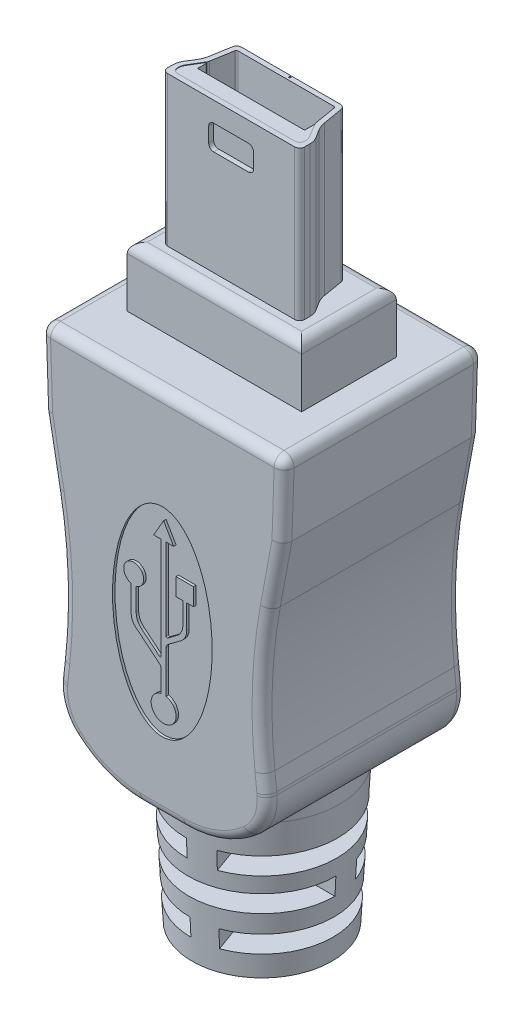
SolidWorks part; units mm, degrees
ref_plane "Front Plane" through (0, 0, 0) normal (0, 0, 1) x (1, 0, 0)
ref_plane "Top Plane" through (0, 0, 0) normal (0, 1, 0) x (1, 0, 0)
ref_plane "Right Plane" through (0, 0, 0) normal (1, 0, 0) x (0, 0, -1)
sketch "Sketch1" plane through (0, 0, 0) normal (0, 0, 1) x (1, 0, 0)
  line L0 (-1.1038, 0) -> (1.1038, 0)
  line L2 (5.3251, 3.5365) -> (5.2287, 4.4229)
  line L3 (-6.223, 18.796) -> (-6.096, 14.986)
  line L4 (-6.096, 14.986) -> (-5.5046, 11.7926)
  line L5 (6.223, 18.796) -> (-6.223, 18.796)
  line L6 (0, 0) -> (0, 13.2322) construction
  line L8 (-5.3251, 3.5365) -> (-5.2287, 4.4229)
  line L9 (6.223, 18.796) -> (6.096, 14.986)
  line L10 (6.096, 14.986) -> (5.5046, 11.7926)
  arc A0 (5.2287, 4.4229) -> (5.5046, 11.7926) centre (30.48, 7.1676) cw
  arc A1 (-5.2287, 4.4229) -> (-5.5046, 11.7926) centre (-30.48, 7.1676) ccw
  arc A2 (1.1038, 0) -> (4.5089, 1.3102) centre (1.1038, 5.08) ccw
  arc A3 (-4.5089, 1.3102) -> (-1.1038, 0) centre (-1.1038, 5.08) ccw
  arc A4 (5.3378, 3.4027) -> (5.3251, 3.5365) centre (0.2748, 2.9876) ccw
  arc A5 (-5.3378, 3.4027) -> (-5.3251, 3.5365) centre (-0.2748, 2.9876) cw
  arc A6 (-5.3378, 3.4027) -> (-4.5089, 1.3102) centre (-2.8063, 3.1951) ccw
  arc A7 (4.5089, 1.3102) -> (5.3378, 3.4027) centre (2.8063, 3.1951) ccw
  point P14 (0, 18.796)
  point P16 (4.5971, 1.1293)
  point P17 (4.826, 8.128)
  point P20 (-4.826, 8.128)
  point P23 (4.5554, 0)
  point P26 (-4.5554, 0)
  point P29 (5.461, 2.286)
  point P32 (-5.461, 2.286)
  dimension "D9" = 25.4
  dimension "D10" = 5.08
  dimension "D7" = 2.54
  dimension "D1" = 9.652
  dimension "D2" = 12.446
  dimension "D3" = 12.192
  dimension "D4" = 3.81
  dimension "D5" = 18.796
  dimension "D6" = 10.922
  dimension "D8" = 2.286
extrude "Boss-Extrude1" add sketch "Sketch1" along normal blind 10.16
fillet "Fillet1" radius 0.508 34 edges at (6.223, 18.796, 5.08) (-6.223, 18.796, 5.08) (6.1595, 16.891, 0) (0, 18.796, 0) (-6.1595, 16.891, 0) (-5.8003, 13.3893, 0) (-5.0978, 8.1178, 0) (-5.2769, 3.9797, 0) (-5.3319, 3.4696, 0) (-2.928, 0.3389, 0) (0, 0, 0) (2.928, 0.3389, 0) (5.3319, 3.4696, 0) (5.2769, 3.9797, 0) (5.0978, 8.1178, 0) (5.8003, 13.3893, 0) (5.0978, 8.1178, 10.16) (5.2769, 3.9797, 10.16) (5.3319, 3.4696, 10.16) (2.928, 0.3389, 10.16) (0, 0, 10.16) (-2.928, 0.3389, 10.16) (-5.3319, 3.4696, 10.16) (-5.2769, 3.9797, 10.16) (-5.0978, 8.1178, 10.16) (-5.8003, 13.3893, 10.16) (-6.1595, 16.891, 10.16) (0, 18.796, 10.16) (6.1595, 16.891, 10.16) (5.8003, 13.3893, 10.16) (-5.1678, 2.2596, 0) (5.1678, 2.2596, 0) (5.1678, 2.2596, 10.16) (-5.1678, 2.2596, 10.16)
sketch "Sketch2" plane through (0, 0, 0) normal (0, 0, -1) x (-1, 0, 0)
  ellipse E0 centre (0, 8.636) end of major axis (0, 3.556) minor radius 2.54
  dimension "D1" = 10.16
  dimension "D2" = 5.08
  dimension "D3" = 3.556
extrude "Cut-Extrude1" cut sketch "Sketch2" against normal blind 0.127
ref_plane "Plane1" through (0, 0, 5.08) normal (0, 0, -1) x (-1, 0, 0)
mirror "Mirror1" about plane through (0, 0, 5.08) normal (0, 0, -1) of "Cut-Extrude1"
sketch "Sketch3" plane through (0, 0, 10.033) normal (0, 0, 1) x (1, 0, 0)
  line L0 (0.0639, 12.685) -> (0.0639, 4.5092) construction
  line L1 (0.0639, 13.1276) -> (-0.4441, 12.2477)
  line L2 (0.6989, 10.9791) -> (1.5879, 10.9791)
  line L3 (0.6989, 10.9791) -> (0.6989, 10.0901)
  line L4 (0.6989, 10.5346) -> (1.5879, 10.5346) construction
  line L5 (0.6989, 10.0901) -> (1.0469, 10.0901)
  line L6 (1.5879, 10.9791) -> (1.5879, 10.0901)
  line L7 (-0.0631, 5.4334) -> (-0.0631, 6.5244)
  line L8 (0.1909, 5.4334) -> (0.1909, 7.5804)
  line L9 (-0.4441, 12.2477) -> (-0.0631, 12.2477)
  line L10 (0.5719, 12.2477) -> (0.0639, 13.1276)
  line L11 (0.0639, 13.1276) -> (0.0639, 12.7432) construction
  line L12 (1.0469, 10.0901) -> (1.2399, 10.0901) construction
  line L13 (0.272, 8.0523) -> (0.7391, 8.3989)
  line L14 (1.2399, 10.0901) -> (1.2399, 8.8701)
  line L15 (0.932, 8.2582) -> (0.2935, 7.7844)
  line L16 (-0.1463, 7.0423) -> (-1.0566, 7.7949)
  line L17 (-1.3331, 8.3822) -> (-1.3331, 9.5347)
  line L18 (-1.5871, 8.8632) -> (-1.3331, 8.8632) construction
  line L19 (-0.1552, 6.7202) -> (-1.3659, 7.721)
  line L20 (-1.5871, 8.1908) -> (-1.5871, 9.5347)
  line L21 (-1.4601, 8.8632) -> (-1.4601, 9.2602) construction
  line L22 (1.0469, 10.0901) -> (1.0469, 9.0108)
  line L23 (0.1909, 8.1908) -> (-0.0631, 8.1908) construction
  line L24 (0.0639, 8.1908) -> (0.0639, 8.5498) construction
  line L25 (0.1909, 12.2477) -> (0.5719, 12.2477)
  line L26 (1.2399, 10.0901) -> (1.5879, 10.0901)
  line L27 (-0.0631, 7.0814) -> (-0.0631, 12.2477)
  line L28 (0.1909, 8.0931) -> (0.1909, 12.2477)
  line L29 (1.1434, 10.0901) -> (1.1434, 10.172) construction
  line L30 (1.1434, 10.5346) -> (1.1434, 10.4705) construction
  arc A0 (-0.0631, 5.4334) -> (0.1909, 5.4334) centre (0.0639, 4.8112) ccw
  arc A1 (-1.3331, 9.5347) -> (-1.5871, 9.5347) centre (-1.4601, 10.0266) ccw
  arc A2 (1.2399, 8.8701) -> (0.932, 8.2582) centre (0.4779, 8.8701) cw
  arc A3 (1.0469, 9.0108) -> (0.7391, 8.3989) centre (0.2849, 9.0108) cw
  arc A4 (-1.3331, 8.3822) -> (-1.0566, 7.7949) centre (-0.5711, 8.3822) ccw
  arc A5 (-1.5871, 8.1908) -> (-1.3659, 7.721) centre (-0.9775, 8.1908) ccw
  arc A6 (-0.0631, 7.0814) -> (-0.1463, 7.0423) centre (-0.1139, 7.0814) cw
  arc A7 (0.1909, 8.0931) -> (0.272, 8.0523) centre (0.2417, 8.0931) ccw
  arc A8 (0.2935, 7.7844) -> (0.1909, 7.5804) centre (0.4449, 7.5804) ccw
  arc A9 (-0.0631, 6.5244) -> (-0.1552, 6.7202) centre (-0.3171, 6.5244) ccw
  point P2 (0.0081, 8.6549)
  dimension "D1" = 1.27
  dimension "D2" = 1.016
  dimension "D12" = 0.762
  dimension "D15" = 0.762
  dimension "D17" = 0.762
  dimension "D19" = 0.0508
  dimension "D20" = 0.254
  dimension "D3" = 0.889
  dimension "D4" = 0.889
  dimension "D5" = 1.016
  dimension "D6" = 1.016
  dimension "D7" = 1.016
  dimension "D8" = 0.508
  dimension "D9" = 1.397
  dimension "D10" = 0.508
  dimension "D11" = 0.254
  dimension "D13" = 0.254
  dimension "D14" = 50.42
  dimension "D18" = 0.254
extrude "Boss-Extrude2" add sketch "Sketch3" along normal blind 0.127
sketch "Sketch5" plane through (0, 0, 0) normal (0, -1, 0) x (1, 0, 0)
  line L0 (0, 9.652) -> (0, 0.508) construction
  line L1 (1.1038, 9.652) -> (-1.1038, 9.652) construction
  line L2 (-1.1038, 0.508) -> (1.1038, 0.508) construction
  circle A0 centre (0, 5.08) radius 3.937
  dimension "D1" = 7.874
extrude "Boss-Extrude3" add sketch "Sketch5" along normal blind 7.112 draft 3 and the other way blind 1.143
ref_axis "Axis1" through (0, 0, 5.08) along (0, -1, 0)
sketch "Sketch6" plane through (0, 0, 0) normal (1, 0, 0) x (0, 0, -1)
  line L0 (-5.08, 0) -> (-5.08, -7.112) construction
  line L1 (-7.366, -2.4384) -> (-11.069, -2.4384)
  line L2 (-7.366, -2.4384) -> (-7.366, -1.524)
  line L3 (-7.366, -1.524) -> (-11.069, -1.524)
  line L4 (-11.069, -2.4384) -> (-11.069, -1.524)
  line L5 (-2.794, -2.4384) -> (1.3873, -2.4384)
  line L6 (-2.794, -2.4384) -> (-2.794, -1.524)
  line L7 (-2.794, -1.524) -> (1.3873, -1.524)
  line L8 (1.3873, -2.4384) -> (1.3873, -1.524)
  line L9 (-8.8591, 0) -> (-1.3009, 0) construction
  line L11 (-2.794, -5.1054) -> (0.7668, -5.1054)
  line L12 (-2.794, -5.1054) -> (-2.794, -6.0198)
  line L13 (-2.794, -6.0198) -> (0.7668, -6.0198)
  line L14 (0.7668, -5.1054) -> (0.7668, -6.0198)
  line L15 (-7.366, -5.1054) -> (-10.6323, -5.1054)
  line L16 (-7.366, -5.1054) -> (-7.366, -6.0198)
  line L17 (-7.366, -6.0198) -> (-10.6323, -6.0198)
  line L18 (-10.6323, -5.1054) -> (-10.6323, -6.0198)
  dimension "D1" = 2.286
  dimension "D2" = 2.286
  dimension "D3" = 1.524
  dimension "D4" = 1.524
  dimension "D5" = 0.9144
  dimension "D6" = 0.9144
  dimension "D7" = 0.9144
  dimension "D8" = 0.9144
  dimension "D9" = 2.667
  dimension "D10" = 2.667
  dimension "D11" = 2.286
  dimension "D12" = 2.286
revolve "Cut-Revolve1" cut sketch "Sketch6" angle 160 about axis through (0, 0, 5.08) along (0, -1, 0)
sketch "Sketch7" plane through (0, 0, 5.08) normal (0, 0, -1) x (-1, 0, 0)
  line L0 (3.8092, -2.4384) -> (0, -2.4384) construction
  line L1 (-2.286, -3.2512) -> (-5.6214, -3.2512)
  line L2 (-2.286, -3.2512) -> (-2.286, -4.1656)
  line L3 (-2.286, -4.1656) -> (-5.6214, -4.1656)
  line L4 (-5.6214, -3.2512) -> (-5.6214, -4.1656)
  line L5 (2.286, -3.2512) -> (5.8067, -3.2512)
  line L6 (2.286, -3.2512) -> (2.286, -4.1656)
  line L7 (2.286, -4.1656) -> (5.8067, -4.1656)
  line L8 (5.8067, -3.2512) -> (5.8067, -4.1656)
  line L9 (0, -2.4384) -> (-3.8092, -2.4384) construction
  line L10 (0, 0) -> (0, -7.112) construction
  dimension "D1" = 0.9144
  dimension "D2" = 0.9144
  dimension "D3" = 0.8128
  dimension "D4" = 0.8128
  dimension "D5" = 2.286
  dimension "D6" = 2.286
revolve "Cut-Revolve2" cut sketch "Sketch7" angle 160 about axis through (0, 0, 5.08) along (0, -1, 0)
sketch "Sketch8" plane through (0, 18.796, 0) normal (0, 1, 0) x (1, 0, 0)
  line L0 (-5.6978, -5.08) -> (-2.3849, -5.08) construction
  line L1 (-4.445, -2.6796) -> (4.445, -2.6796)
  line L2 (-4.445, -2.6796) -> (-4.445, -7.5056)
  line L3 (-4.445, -7.5056) -> (4.445, -7.5056)
  line L4 (4.445, -2.6796) -> (4.445, -7.5056)
  line L5 (-5.6978, -0.508) -> (-5.6978, -9.652) construction
  line L6 (4.445, -5.0926) -> (3.1929, -5.0926) construction
  line L7 (0, -0.508) -> (0, -1.2138) construction
  line L8 (5.6978, -0.508) -> (-5.6978, -0.508) construction
  line L9 (0, -7.5056) -> (0, -6.276) construction
  dimension "D1" = 8.89
  dimension "D2" = 4.826
extrude "Boss-Extrude4" add sketch "Sketch8" along normal blind 3.048
fillet "Fillet2" radius 0.508 4 edges at (0, 21.844, 2.6796) (4.445, 21.844, 5.0926) (0, 21.844, 7.5056) (-4.445, 21.844, 5.0926)
sketch "Sketch9" plane through (0, 21.844, 0) normal (0, 1, 0) x (1, 0, 0)
  line L0 (-3.4504, -5.0926) -> (-2.8204, -5.0926) construction
  line L1 (-2.5164, -3.6058) -> (2.5164, -3.6058)
  line L2 (-3.4927, -6.1299) -> (-3.4927, -6.3998)
  line L3 (0, -6.6538) -> (3.2387, -6.6538)
  line L4 (0, -6.6538) -> (-3.2387, -6.6538)
  line L5 (0, -3.6058) -> (0, -4.6543) construction
  line L6 (0, -3.1876) -> (0, -3.6834) construction
  line L7 (3.937, -3.1876) -> (-3.937, -3.1876) construction
  line L8 (-3.937, -5.0926) -> (-3.4504, -5.0926) construction
  line L9 (-3.937, -3.1876) -> (-3.937, -6.9976) construction
  line L10 (-2.7668, -3.817) -> (-2.9417, -4.8408)
  line L11 (-3.4927, -5.1298) -> (-3.4927, -6.6538) construction
  line L12 (-3.1218, -5.3082) -> (-3.3649, -5.6908)
  line L13 (3.4927, -6.1299) -> (3.4927, -6.3998)
  line L14 (3.1218, -5.3082) -> (3.3649, -5.6908)
  line L15 (2.7668, -3.817) -> (2.9417, -4.8408)
  line L16 (-2.4521, -3.8598) -> (2.4521, -3.8598)
  line L17 (2.5272, -3.9231) -> (2.727, -5.0926)
  line L18 (-2.727, -5.0926) -> (-2.727, -5.6378)
  line L19 (-2.5272, -3.9231) -> (-2.727, -5.0926)
  line L20 (-2.727, -5.6378) -> (2.727, -5.6378)
  line L21 (2.727, -5.6378) -> (2.727, -5.0926)
  arc A0 (3.2387, -6.6538) -> (3.4927, -6.3998) centre (3.2387, -6.3998) ccw
  arc A1 (2.7668, -3.817) -> (2.5164, -3.6058) centre (2.5164, -3.8598) ccw
  arc A2 (-3.4927, -6.3998) -> (-3.2387, -6.6538) centre (-3.2387, -6.3998) ccw
  arc A3 (-2.7668, -3.817) -> (-2.5164, -3.6058) centre (-2.5164, -3.8598) cw
  arc A4 (2.4521, -3.8598) -> (2.5272, -3.9231) centre (2.4521, -3.936) cw
  arc A5 (-2.5272, -3.9231) -> (-2.4521, -3.8598) centre (-2.4521, -3.936) cw
  arc A6 (3.1218, -5.3082) -> (2.9417, -4.8408) centre (4.1935, -4.6269) cw
  arc A7 (-2.9417, -4.8408) -> (-3.1218, -5.3082) centre (-4.1935, -4.6269) cw
  arc A8 (3.4927, -6.1299) -> (3.3649, -5.6908) centre (2.6741, -6.1299) ccw
  arc A9 (-3.3649, -5.6908) -> (-3.4927, -6.1299) centre (-2.6741, -6.1299) ccw
  point P30 (3.4927, -6.6538)
  point P33 (2.7307, -3.6058)
  point P39 (-2.7307, -3.6058)
  point P46 (2.9847, -5.0926)
  point P49 (-2.9847, -5.0926)
  point P52 (3.4927, -5.8918)
  point P55 (-3.4927, -5.8918)
  dimension "D7" = 0.254
  dimension "D8" = 0.0762
  dimension "D9" = 1.27
  dimension "D10" = 0.8186
  dimension "D1" = 0.254
  dimension "D2" = 0.254
  dimension "D3" = 0.762
  dimension "D4" = 0.254
  dimension "D5" = 0.254
  dimension "D6" = 1.016
extrude "Boss-Extrude5" add sketch "Sketch9" along normal blind 7.62 separate body
sketch "Sketch10" plane through (0, 29.464, 0) normal (0, 1, 0) x (1, 0, 0)
  line L0 (-2.727, -5.0926) -> (-3.166, -5.8219)
  line L1 (-3.2387, -6.0839) -> (-3.2387, -6.1458)
  line L2 (-2.9847, -6.3998) -> (2.9847, -6.3998)
  line L3 (0, -6.3998) -> (0, -4.3507) construction
  line L4 (3.2387, -6.0839) -> (3.2387, -6.1458)
  line L5 (2.727, -5.0926) -> (-2.727, -5.0926)
  line L6 (2.727, -5.0926) -> (3.166, -5.8219)
  line L11 (-3.2387, -6.6538) -> (3.2387, -6.6538) construction
  arc A0 (3.2387, -6.1458) -> (2.9847, -6.3998) centre (2.9847, -6.1458) cw
  arc A1 (-3.2387, -6.1458) -> (-2.9847, -6.3998) centre (-2.9847, -6.1458) ccw
  arc A2 (-3.166, -5.8219) -> (-3.2387, -6.0839) centre (-2.7307, -6.0839) ccw
  arc A3 (3.2387, -6.0839) -> (3.166, -5.8219) centre (2.7307, -6.0839) ccw
  point P15 (0, -5.0926)
  point P20 (-3.2387, -5.9428)
  point P23 (3.2387, -5.9428)
  dimension "D1" = 0.508
  dimension "D3" = 0.254
extrude "Cut-Extrude2" cut sketch "Sketch10" against normal blind 0.0254
sketch "Sketch11" plane through (0, 29.4386, 0) normal (0, 1, 0) x (1, 0, 0)
  line L0 (-2.765, -5.1557) -> (-2.727, -5.1557)
  line L1 (-2.727, -5.0926) -> (-3.166, -5.8219) construction
  line L2 (-2.765, -5.1557) -> (-2.727, -5.0926)
  line L3 (-2.727, -5.0926) -> (-2.727, -5.1557)
  line L4 (-2.727, -5.0926) -> (-2.727, -5.6378) construction
  line L5 (2.727, -5.0926) -> (2.765, -5.1557)
  line L6 (3.166, -5.8219) -> (2.727, -5.0926) construction
  line L7 (2.727, -5.0926) -> (2.727, -5.1557)
  line L8 (2.727, -5.1557) -> (2.765, -5.1557)
extrude "Cut-Extrude3" cut sketch "Sketch11" against normal up to surface (7.5946 mm away) up to face at (0, 21.844, 5.0926)
fillet "Fillet3" radius 0.254 2 edges at (-2.727, 25.654, 5.0926) (2.727, 25.654, 5.0926)
fillet "Fillet4" radius 0.0508 2 edges at (2.727, 25.6413, 5.1557) (-2.727, 25.6413, 5.1557)
sketch "Sketch12" plane through (0, 0, 6.6538) normal (0, 0, 1) x (1, 0, 0)
  line L0 (-3.2387, 29.464) -> (3.2387, 29.464) construction
  line L1 (-0.889, 27.178) -> (0.889, 27.178)
  line L2 (-1.143, 27.432) -> (-1.143, 28.194)
  line L3 (-0.889, 28.448) -> (0.889, 28.448)
  line L4 (1.143, 27.432) -> (1.143, 28.194)
  line L5 (0, 29.464) -> (0, 29.0468) construction
  line L6 (0, 28.448) -> (0, 27.9499) construction
  arc A0 (0.889, 28.448) -> (1.143, 28.194) centre (0.889, 28.194) cw
  arc A1 (0.889, 27.178) -> (1.143, 27.432) centre (0.889, 27.432) ccw
  arc A2 (-0.889, 27.178) -> (-1.143, 27.432) centre (-0.889, 27.432) cw
  arc A3 (-0.889, 28.448) -> (-1.143, 28.194) centre (-0.889, 28.194) ccw
  point P13 (1.143, 28.448)
  point P16 (1.143, 27.178)
  point P19 (-1.143, 27.178)
  dimension "D4" = 0.254
  dimension "D1" = 2.286
  dimension "D2" = 1.27
  dimension "D3" = 1.016
extrude "Cut-Extrude4" cut sketch "Sketch12" against normal blind 0.254
sketch "Sketch13" plane through (0, 0, 5.6378) normal (0, 0, -1) x (-1, 0, 0)
  line L0 (2.727, 21.844) -> (-2.727, 21.844)
  line L1 (-2.727, 29.1784) -> (-1.711, 29.1784)
  line L2 (2.0666, 27.9462) -> (2.0666, 29.153)
  line L3 (1.838, 29.1784) -> (1.838, 27.9716)
  line L4 (1.838, 27.9716) -> (-1.711, 27.9716)
  line L5 (-1.711, 27.9716) -> (-1.711, 29.1784)
  line L6 (1.838, 29.1784) -> (2.727, 29.1784)
  line L7 (1.8634, 27.9462) -> (1.8634, 29.153)
  line L9 (2.0666, 21.8694) -> (1.8634, 21.8694)
  line L10 (2.0666, 21.8694) -> (2.0666, 27.9462)
  line L12 (1.8634, 21.8694) -> (1.8634, 27.9462)
  line L15 (1.1159, 21.8694) -> (1.1159, 27.9462)
  line L16 (1.1159, 27.9462) -> (0.9127, 27.9462)
  line L17 (0.9127, 21.8694) -> (0.9127, 27.9462)
  line L18 (1.1159, 21.8694) -> (0.9127, 21.8694)
  line L23 (0.1651, 21.8694) -> (0.1651, 27.9462)
  line L24 (0.1651, 27.9462) -> (-0.0381, 27.9462)
  line L25 (-0.0381, 21.8694) -> (-0.0381, 27.9462)
  line L26 (0.1651, 21.8694) -> (-0.0381, 21.8694)
  line L31 (-0.7857, 21.8694) -> (-0.7857, 27.9462)
  line L32 (-0.7857, 27.9462) -> (-0.9889, 27.9462)
  line L33 (-0.9889, 21.8694) -> (-0.9889, 27.9462)
  line L34 (-0.7857, 21.8694) -> (-0.9889, 21.8694)
  line L39 (-1.7364, 21.8694) -> (-1.7364, 27.9462)
  line L41 (-1.9396, 21.8694) -> (-1.9396, 27.9462)
  line L42 (-1.7364, 21.8694) -> (-1.9396, 21.8694)
  line L44 (-2.727, 29.4386) -> (-2.727, 21.844) construction
  line L46 (2.0666, 29.153) -> (1.8634, 29.153)
  line L47 (2.727, 29.1784) -> (2.727, 21.844)
  line L49 (-2.727, 29.1784) -> (-2.727, 21.844)
  line L50 (-1.7364, 27.9462) -> (-1.7364, 29.153)
  line L51 (-1.7364, 29.153) -> (-1.9396, 29.153)
  line L52 (-1.9396, 29.153) -> (-1.9396, 27.9462)
  dimension "D1" = 0.0254
  dimension "D2" = 0.0254
  dimension "D3" = 0.0254
  dimension "D7" = 5
extrude "Cut-Extrude5" cut sketch "Sketch13" against normal blind 0.127
fillet "Fillet5" radius 0.1016 10 edges at (0.7857, 24.9078, 5.6378) (0.9889, 24.9078, 5.6378) (1.7364, 25.5112, 5.6378) (1.9396, 25.5112, 5.6378) (0.0381, 24.9078, 5.6378) (-0.1651, 24.9078, 5.6378) (-0.9127, 24.9078, 5.6378) (-1.1159, 24.9078, 5.6378) (-2.0666, 25.5112, 5.6378) (-1.8634, 25.5112, 5.6378)
sketch "Sketch14" plane through (0, 0, 3.6058) normal (0, 0, -1) x (-1, 0, 0)
  line L0 (0, 21.844) -> (0, 24.7251)
  line L1 (-2.5164, 21.844) -> (2.5164, 21.844) construction
  line L2 (0.1789, 24.8752) -> (0.5235, 24.8144)
  line L3 (0.762, 25.0145) -> (0.762, 26.8162)
  line L4 (0.5235, 27.0163) -> (0.1789, 26.9555)
  line L5 (0, 27.1056) -> (0, 29.464)
  line L6 (-2.5164, 29.464) -> (2.5164, 29.464) construction
  line L7 (-0.0762, 21.844) -> (-0.0762, 24.7554)
  line L8 (0.1623, 24.9555) -> (0.5069, 24.8947)
  line L9 (0.6858, 25.0448) -> (0.6858, 26.7859)
  line L10 (0.5069, 26.936) -> (0.1623, 26.8752)
  line L11 (-0.0762, 27.0754) -> (-0.0762, 29.464)
  line L12 (-0.0762, 29.464) -> (0, 29.464)
  line L13 (-0.0762, 21.844) -> (0, 21.844)
  arc A0 (-0.0762, 24.7554) -> (0.1623, 24.9555) centre (0.127, 24.7554) cw
  arc A1 (0.5235, 24.8144) -> (0.762, 25.0145) centre (0.5588, 25.0145) ccw
  arc A2 (0.762, 26.8162) -> (0.5235, 27.0163) centre (0.5588, 26.8162) ccw
  arc A3 (0.1623, 26.8752) -> (-0.0762, 27.0754) centre (0.127, 27.0754) cw
  arc A4 (0, 24.7251) -> (0.1789, 24.8752) centre (0.1524, 24.7251) cw
  arc A5 (0.5069, 24.8947) -> (0.6858, 25.0448) centre (0.5334, 25.0448) ccw
  arc A6 (0.6858, 26.7859) -> (0.5069, 26.936) centre (0.5334, 26.7859) ccw
  arc A7 (0.1789, 26.9555) -> (0, 27.1056) centre (0.1524, 27.1056) cw
  point P21 (0.762, 24.7724)
  point P24 (0.762, 27.0584)
  point P35 (0, 26.924)
  dimension "D11" = 0.2032
  dimension "D12" = 0.1524
  dimension "D1" = 80
  dimension "D2" = 80
  dimension "D3" = 0.762
  dimension "D4" = 2.286
  dimension "D5" = 2.54
  dimension "D6" = 0.0762
  dimension "D7" = 0.0762
  dimension "D8" = 0.0762
  dimension "D9" = 0.0762
  dimension "D10" = 0.0762
extrude "Cut-Extrude6" cut sketch "Sketch14" against normal blind 0.127
